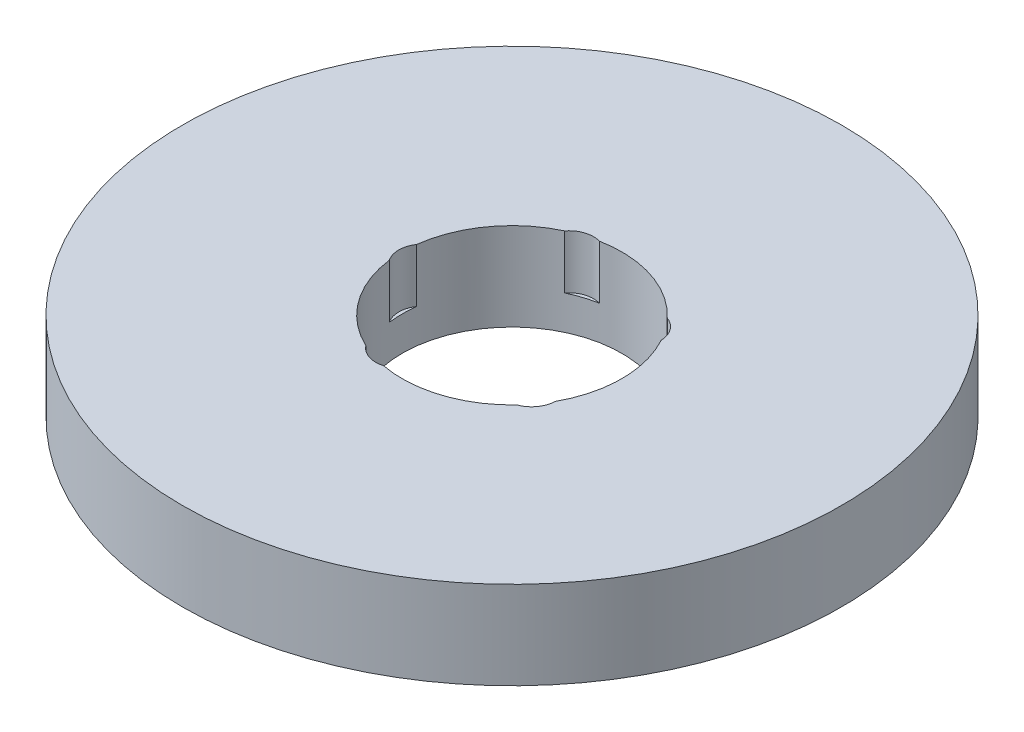
SolidWorks part; units mm, degrees
ref_plane "Front Plane" through (0, 0, 0) normal (0, 0, 1) x (1, 0, 0)
ref_plane "Top Plane" through (0, 0, 0) normal (0, 1, 0) x (1, 0, 0)
ref_plane "Right Plane" through (0, 0, 0) normal (1, 0, 0) x (0, 0, -1)
sketch "Sketch1" plane through (0, 0, 0) normal (0, 1, 0) x (1, 0, 0)
  circle A0 centre (0, 0) radius 60
  dimension "FLANGE_OD" = 120
extrude "Boss-Extrude1" add sketch "Sketch1" along normal blind 16
sketch "Sketch2" plane through (0, 0, 0) normal (0, 1, 0) x (1, 0, 0)
  circle A0 centre (0, 0) radius 20
  dimension "BORE_D" = 40
extrude "Cut-Extrude1" cut sketch "Sketch2" along normal through all
sketch "Sketch3" plane through (0, 16, 0) normal (0, 1, 0) x (1, 0, 0)
  circle A0 centre (0, 0) radius 16.1619 construction
  circle A1 centre (-16.1619, 0) radius 4.4502
  dimension "BOLT_D" = 8.9005
  dimension "BOLT_PCD" = 32.3238
extrude "Cut-Extrude2" cut sketch "Sketch3" against normal blind 9.7875
pattern_circular "CirPattern1" count 5 over 360 about axis through (0, 0, 0) along (0, 1, 0) of "Cut-Extrude2"
